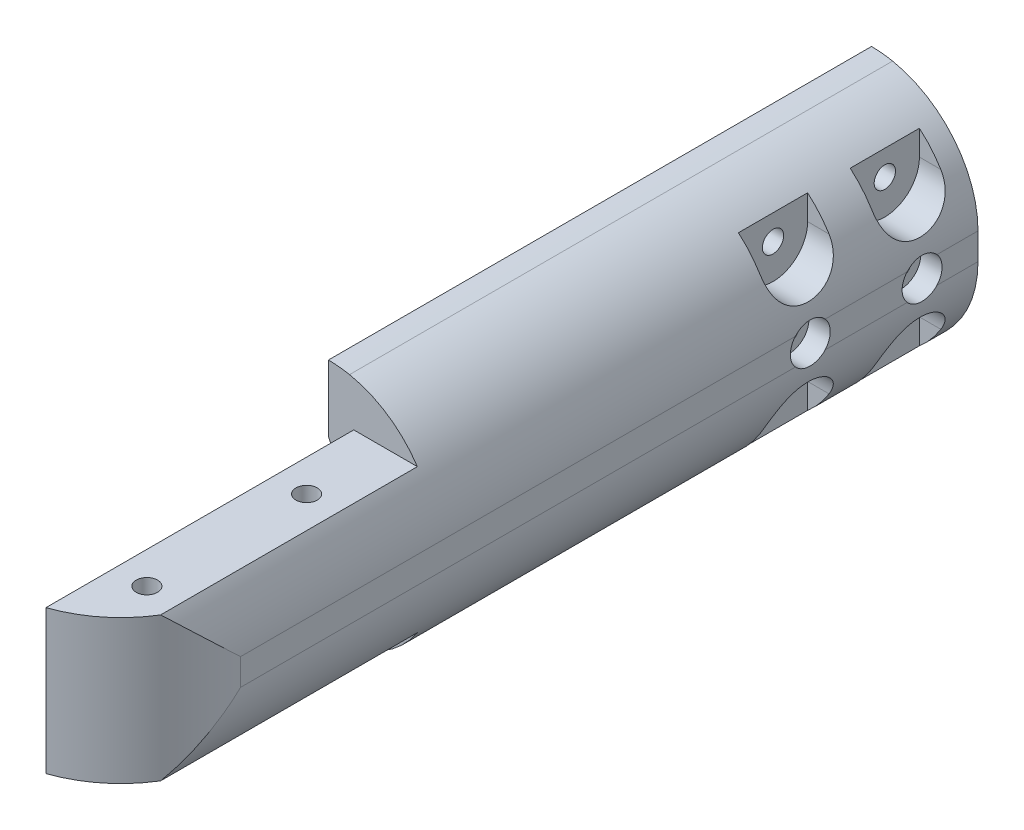
SolidWorks part; units mm, degrees
material "1060 Alloy"
ref_plane "Front Plane" through (0, 0, 0) normal (0, 0, 1) x (1, 0, 0)
ref_plane "Top Plane" through (0, 0, 0) normal (0, 1, 0) x (1, 0, 0)
ref_plane "Right Plane" through (0, 0, 0) normal (1, 0, 0) x (0, 0, -1)
sketch "Sketch1" plane through (0, 0, 0) normal (0, 0, 1) x (1, 0, 0)
  line L0 (0, 22.5) -> (0, -22.5) construction
  line L1 (0.25, 22.5) -> (0.25, 9.9969)
  line L2 (0.25, -9.9969) -> (0.25, -22.5)
  line L4 (0.25, 22.5) -> (0.25, -22.5) construction
  arc A0 (0, -22.5) -> (0, 22.5) centre (0, 0) ccw
  arc A1 (0, -10) -> (0, 10) centre (0, 0) ccw
  dimension "D1" = 20
  dimension "D2" = 45
  dimension "D3" = 0.25
extrude "Boss-Extrude1" add sketch "Sketch1" along normal blind 40 contours A1 L2 A0 L1 region at (10.9613, 0, 0)
sketch "Sketch5" plane through (0, 0, 40) normal (0, 0, 1) x (1, 0, 0)
  line L0 (0.25, -22.5) -> (0.25, 8.9826)
  line L1 (0.25, -22.5) -> (22.5, -22.5)
  line L2 (22.5, -22.5) -> (22.5, 22.4986)
  line L3 (22.5, 22.4986) -> (0.25, 22.4986)
  line L4 (0.25, 22.4986) -> (0.25, 8.9826)
  line L7 (0.25, 22.4986) -> (0.25, 9.9969)
  line L9 (0.25, -9.9969) -> (0.25, -22.4986) construction
  circle A0 centre (-16.4925, 0) radius 19 construction
  arc A1 (0.25, -9.9969) -> (0.25, 9.9969) centre (0, 0) ccw construction
  arc A2 (0.25, -9.9969) -> (0.25, 9.9969) centre (-16.4925, 0) ccw
  arc A3 (0.25, -22.4986) -> (0.25, 22.4986) centre (0, 0) ccw construction
  circle A4 centre (-16.4925, 0) radius 19.5 construction
  point P2 (-17.4018, 3.4045)
  point P3 (-12.3075, 2.8559)
  point P4 (0.25, -3.0613)
  point P5 (-13.6007, 0.7006)
  point P14 (0.25, 9.9969)
  point P18 (0.25, -9.9969)
  point P20 (10.895, 4.2)
  point P24 (-16.4613, 0)
  arc M21 (0.25, -22.4986) -> (0.25, 22.4986) centre (0, 0) ccw
  line M22 (0.25, 22.4986) -> (0.25, 9.9969)
  arc M23 (0.25, 9.9969) -> (0.25, -9.9969) centre (0, 0) cw
  dimension "D2" = 38
  dimension "D1" = 0.5
extrude "Boss-Extrude4" add sketch "Sketch5" along normal blind 62 contours A2 L0 | M22 M23 M21 region at (10.9613, 0, 40) region at (5.3611, 0, 40)
sketch "Sketch3" plane through (0, 0, 102) normal (0, 0, 1) x (1, 0, 0)
  line L0 (18, 22.5) -> (18, -22.5)
  line L1 (5, -22.5) -> (5, 22.5)
  line L2 (5, 22.5) -> (22.5, 22.5) construction
  line L3 (22.5, 22.5) -> (22.5, -22.5) construction
  line L4 (22.5, -22.5) -> (5, -22.5) construction
  line L5 (5, 13.5) -> (22.5, 13.5)
  line L6 (5, -13.5) -> (22.5, -13.5)
  line L7 (0, 0) -> (22.5, 0) construction
  circle A0 centre (0, 0) radius 10 construction
  arc A3 (0.25, -22.4986) -> (0.25, 22.4986) centre (0, 0) ccw construction
  arc A6 (0.25, -22.4986) -> (0.25, 22.4986) centre (0, 0) ccw construction
  arc A7 (0.25, -9.9969) -> (0.25, 9.9969) centre (0, 0) ccw construction
  point P13 (5, 0)
  point P23 (18, 13.5)
  arc M41 (0.25, -22.4986) -> (0.25, 22.4986) centre (0, 0) ccw
  dimension "D1" = 17.5
  dimension "D2" = 9
extrude "Boss-Extrude5" add sketch "Sketch3" along normal blind 59 contours L1 L6 L0 L5 | L0 M41 region at (19.8164, 0, 102) region at (11.5, 0, 102)
sketch "Sketch6" plane through (0, -13.5, 0) normal (0, -1, 0) x (1, 0, 0)
  circle A0 centre (10.995, 116.85) radius 2
  circle A1 centre (10.995, 116.85) radius 2 construction
  circle A2 centre (10.995, 146.85) radius 2
  circle A3 centre (10.995, 146.85) radius 2 construction
extrude "Cut-Extrude1" cut sketch "Sketch6" against normal through all
sketch "Sketch8" plane through (0, 0, 0) normal (0, 0, -1) x (-1, 0, 0)
  line L0 (-20.25, 2.4986) -> (-20.25, -2.4986)
  line L1 (-0.25, 22.4986) -> (-0.25, 9.9969) construction
  line L2 (-0.25, -9.9969) -> (-0.25, -22.4986) construction
  arc A0 (-0.25, 22.4986) -> (-0.25, -22.4986) centre (0, 0) ccw construction
  arc A1 (-0.25, 22.4986) -> (-20.25, 2.4986) centre (-0.25, 2.4986) ccw
  arc A2 (-20.25, -2.4986) -> (-0.25, -22.4986) centre (-0.25, -2.4986) ccw
  arc A3 (-0.25, 22.4986) -> (-0.25, -22.4986) centre (0, 0) ccw
  arc M4 (-0.25, 22.4986) -> (-0.25, -22.4986) centre (0, 0) ccw
  dimension "D1" = 20
extrude "Cut-Extrude3" cut sketch "Sketch8" against normal through all contours A2 L0 A1 M4 region at (20.7284, 0, 0)
sketch "Sketch7" plane through (0, -13.5, 0) normal (0, -1, 0) x (1, 0, 0)
  line L2 (20.25, 138.5) -> (20.25, 161)
  line L3 (20.25, 161) -> (-2.25, 161)
  line L4 (20.25, 161) -> (20.25, 0) construction
  line L5 (5, 161) -> (16.9524, 161) construction
  arc A0 (20.25, 138.5) -> (-2.25, 161) centre (-2.25, 138.5) ccw
  dimension "D1" = 22.5
extrude "Cut-Extrude2" cut sketch "Sketch7" against normal through all
sketch "Sketch9" plane through (0.25, 0, 0) normal (-1, 0, 0) x (0, 0, 1)
  line L0 (0, 0) -> (159.7999, 0) construction
  line L1 (159.7999, 13.5) -> (159.7999, -13.5) construction
  circle A0 centre (31.5, -13) radius 2
  circle A1 centre (10.5, -13) radius 2
  circle A2 centre (10.5, 13) radius 2
  circle A3 centre (31.5, 13) radius 2
  circle A8 centre (31.5, 0) radius 2
  circle A9 centre (10.5, 0) radius 2
  circle A10 centre (10.5, 13) radius 2 construction
  circle A11 centre (31.5, 13) radius 2 construction
  circle A12 centre (31.5, -13) radius 2 construction
  circle A13 centre (10.5, -13) radius 2 construction
  point P25 (0, 0)
  point P26 (0, 0)
  dimension "D1" = 4
extrude "Cut-Extrude4" cut sketch "Sketch9" against normal through all
sketch "Sketch10" plane through (20.25, 0, 0) normal (1, 0, 0) x (0, 0, -1)
  circle A0 centre (-31.5, 0) radius 3.75
  circle A1 centre (-10.5, 0) radius 3.75
  dimension "D1" = 7.5
extrude "Cut-Extrude5" cut sketch "Sketch10" against normal blind 4
sketch "Sketch11" plane through (20.25, 0, 0) normal (1, 0, 0) x (0, 0, -1)
  line L0 (-4, -13) -> (-4, -19.5)
  line L1 (-4, -19.5) -> (-17, -19.5)
  line L2 (-17, -19.5) -> (-17, -13)
  line L3 (-25, -13) -> (-25, -19.5)
  line L4 (-25, -19.5) -> (-38, -19.5)
  line L5 (-38, -19.5) -> (-38, -13)
  line L6 (0, 0) -> (-138.5, 0) construction
  line L7 (0, 2.4986) -> (0, -2.4986) construction
  line L8 (-138.5, -2.4986) -> (-138.5, 2.4986) construction
  line L9 (-38, 19.5) -> (-38, 13)
  line L10 (-25, 19.5) -> (-38, 19.5)
  line L11 (-25, 13) -> (-25, 19.5)
  line L12 (-17, 19.5) -> (-17, 13)
  line L13 (-4, 19.5) -> (-17, 19.5)
  line L14 (-4, 13) -> (-4, 19.5)
  arc A0 (-4, -13) -> (-17, -13) centre (-10.5, -13) ccw
  arc A1 (-25, -13) -> (-38, -13) centre (-31.5, -13) ccw
  arc A4 (-25, 13) -> (-38, 13) centre (-31.5, 13) cw
  arc A5 (-4, 13) -> (-17, 13) centre (-10.5, 13) cw
  dimension "D1" = 13
extrude "Cut-Extrude6" cut sketch "Sketch11" against normal blind 7
